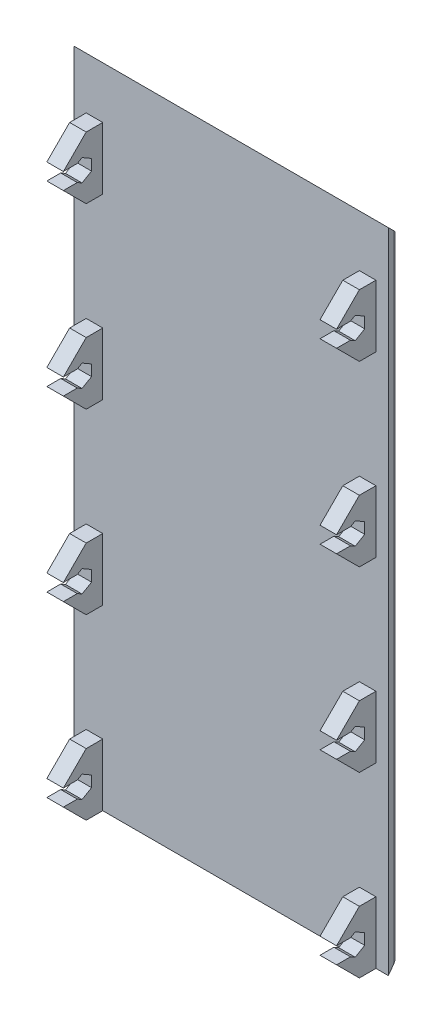
SolidWorks part; units mm, degrees
ref_plane "Front Plane" through (0, 0, 0) normal (0, 0, 1) x (1, 0, 0)
ref_plane "Top Plane" through (0, 0, 0) normal (0, 1, 0) x (1, 0, 0)
ref_plane "Right Plane" through (0, 0, 0) normal (1, 0, 0) x (0, 0, -1)
sketch "Sketch1" plane through (0, 0, 0) normal (0, 1, 0) x (1, 0, 0)
  line L0 (-9.2151, 0) -> (-9.2151, -10)
  line L1 (-9.2151, -10) -> (-5.2151, -10)
  line L2 (-5.2151, -10) -> (-5.2151, 0)
  line L3 (-5.2151, 0) -> (56.7849, 0)
  line L4 (56.7849, 0) -> (56.7849, -10)
  line L5 (56.7849, -10) -> (60.7849, -10)
  line L6 (60.7849, -10) -> (60.7849, 0)
  line L7 (60.7849, 0) -> (63.7849, 0)
  line L8 (-9.2151, 0) -> (-12.2151, 0)
  line L9 (-12.2151, 0) -> (-8.1737, 7)
  line L10 (-8.1737, 7) -> (59.7434, 7)
  line L11 (59.7434, 7) -> (63.7849, 0)
  line L12 (25.7849, 7) -> (25.7849, 0) construction
  dimension "D1" = 3
  dimension "D2" = 10
  dimension "D3" = 70
  dimension "D4" = 7
  dimension "D5" = 4
  dimension "D6" = 60
extrude "Boss-Extrude1" add sketch "Sketch1" along normal blind 156.5
sketch "Sketch4" plane through (60.7849, 0, 0) normal (1, 0, 0) x (0, 0, -1)
  line L0 (0, 156.5) -> (0, 0) construction
  line L1 (-37.5185, 156.5) -> (0, 156.5)
  line L2 (-37.5185, 156.5) -> (-37.5185, 144)
  line L3 (-37.5185, 144) -> (0, 144)
  line L4 (0, 156.5) -> (0, 144)
  line L5 (-37.5185, 156.5) -> (0, 144) construction
  line L6 (-37.5185, 144) -> (0, 156.5) construction
  line L7 (-10, 156.5) -> (0, 156.5) construction
  point P0 (-18.7592, 150.25)
  dimension "D1" = 12.5
extrude "Cut-Extrude1" cut sketch "Sketch4" against normal through all
sketch "Sketch5" plane through (60.7849, 0, 0) normal (1, 0, 0) x (0, 0, -1)
  line L0 (0, 156.5) -> (0, 0) construction
  line L1 (-33.3149, 129) -> (0, 129)
  line L2 (-33.3149, 129) -> (-33.3149, 101)
  line L3 (-33.3149, 101) -> (0, 101)
  line L4 (0, 129) -> (0, 101)
  line L5 (-33.3149, 129) -> (0, 101) construction
  line L6 (-33.3149, 101) -> (0, 129) construction
  line L7 (-10, 144) -> (0, 144) construction
  point P0 (-16.6574, 115)
  dimension "D1" = 28
  dimension "D2" = 15
extrude "Cut-Extrude2" cut sketch "Sketch5" against normal through all
sketch "Sketch6" plane through (0, 0, 0) normal (1, 0, 0) x (0, 0, -1)
  line L0 (-10, 144) -> (-10, 129) construction
  line L1 (-2.7, 137.8279) -> (-5, 139.1558)
  line L2 (-5, 139.1558) -> (-7.3, 137.8279)
  line L3 (-7.3, 137.8279) -> (-7.3, 135.1721)
  line L4 (-7.3, 135.1721) -> (-5, 133.8442)
  line L5 (-5, 133.8442) -> (-2.7, 135.1721)
  line L6 (-2.7, 135.1721) -> (-2.7, 137.8279)
  line L7 (-10, 144) -> (0, 144) construction
  line L8 (-6.15, 138.4919) -> (-10, 138.4919)
  line L9 (-6.15, 134.5081) -> (-10, 134.5081)
  line L10 (-10, 134.5081) -> (-10, 138.4919)
  circle A1 centre (-5, 136.5) radius 2.3 construction
  dimension "D1" = 4.6
  dimension "D2" = 7.5
  dimension "D3" = 5
extrude "Cut-Extrude3" cut sketch "Sketch6" against normal through all and the other way through all contours L10 L9 L4 L3 L2 L8 | L5 L6 L1 L2 L3 L4 region at (0, 136.5, 5) region at (0, 136.5, 8.5351)
pattern_linear "LPattern1" count 4 spacing 43 along (0, -1, 0) of "Cut-Extrude2", "Cut-Extrude3"
chamfer "Chamfer3" distance 7 angle 45 1 edges at (25.7849, 156.5, -7)
fillet "Fillet1" radius 8 2 edges at (-8.1737, 74.75, -7) (59.7434, 74.75, -7)
chamfer "Chamfer5" distance 6 angle 45 16 edges at (58.7849, 43, 10) (58.7849, 144, 10) (58.7849, 129, 10) (-7.2151, 144, 10) (-7.2151, 129, 10) (-7.2151, 101, 10) (-7.2151, 86, 10) (58.7849, 101, 10) (58.7849, 86, 10) (58.7849, 58, 10) (58.7849, 0, 10) (58.7849, 15, 10) (-7.2151, 0, 10) (-7.2151, 15, 10) (-7.2151, 58, 10) (-7.2151, 43, 10)
sketch "Sketch7" plane through (0, 0, -7) normal (0, 0, -1) x (-1, 0, 0)
  line L0 (-11.7849, 94.4158) -> (-39.7849, 94.4158) construction
  line L1 (-11.7849, 94.4158) -> (-11.7849, 55.0842) construction
  line L2 (-39.7849, 94.4158) -> (-39.7849, 55.0842) construction
  line L3 (-11.7849, 55.0842) -> (-39.7849, 55.0842) construction
  line L4 (-11.7849, 94.4158) -> (-11.7849, 87.9932)
  line L5 (-11.7849, 94.4158) -> (-39.7849, 94.4158)
  line L6 (-11.7849, 87.4158) -> (-39.7849, 87.4158) construction
  line L7 (-39.7849, 94.4158) -> (-39.7849, 87.9932)
  line L8 (3.5549, 55.0842) -> (-11.7849, 55.0842) construction
  line L9 (-11.7849, 79.3329) -> (-18.2849, 75.5801)
  line L10 (-12.2849, 87.1271) -> (-25.7849, 79.3329)
  line L11 (-25.7849, 79.3329) -> (-39.2849, 87.1271)
  line L14 (-25.7849, 71.25) -> (-39.2849, 63.4558)
  line L15 (-11.7849, 79.3329) -> (-11.7849, 65.5842)
  line L16 (-39.7849, 62.5897) -> (-39.7849, 55.0842)
  line L17 (-39.7849, 55.0842) -> (-32.7849, 59.1256)
  line L18 (-32.7849, 59.1256) -> (-32.7849, 65.5842)
  line L19 (-18.7849, 74.7141) -> (-18.7849, 65.5842)
  line L20 (-11.7849, 65.5842) -> (-32.7849, 65.5842) construction
  line L21 (-25.7849, 71.25) -> (-25.7849, 65.5842)
  line L22 (-18.7849, 65.5842) -> (-25.7849, 65.5842) construction
  line L23 (-32.7849, 83.3744) -> (-39.2849, 79.6216)
  line L24 (3.5549, 0) -> (3.5549, 149.5) construction
  line L25 (-39.7849, 78.7556) -> (-39.7849, 71.8274)
  line L26 (-25.7849, 79.3329) -> (-32.7849, 75.2915)
  line L27 (-32.7849, 75.2915) -> (-25.7849, 71.25)
  line L28 (-11.7849, 55.0842) -> (-39.7849, 55.0842) construction
  line L29 (-39.7849, 55.0842) -> (-55.1246, 55.0842) construction
  line L30 (-55.1246, 149.5) -> (-55.1246, 0) construction
  line L31 (-11.7849, 149.5) -> (-11.7849, 94.4158) construction
  line L32 (3.5549, 149.5) -> (-55.1246, 149.5) construction
  line L33 (-11.7849, 55.0842) -> (-11.7849, 0) construction
  line L34 (-55.1246, 0) -> (3.5549, 0) construction
  line L35 (-39.2849, 70.9613) -> (-32.7849, 67.2085)
  line L38 (-32.7849, 59.1256) -> (-31.2016, 60.0397)
  arc A0 (-11.7849, 65.5842) -> (-32.7849, 65.5842) centre (-22.2849, 65.5842) cw
  arc A1 (-18.7849, 65.5842) -> (-25.7849, 65.5842) centre (-22.2849, 65.5842) cw
  arc A3 (-18.2849, 75.5801) -> (-18.7849, 74.7141) centre (-17.7849, 74.7141) ccw
  arc A4 (-11.7849, 87.9932) -> (-12.2849, 87.1271) centre (-12.7849, 87.9932) cw
  arc A5 (-39.2849, 87.1271) -> (-39.7849, 87.9932) centre (-38.7849, 87.9932) cw
  arc A7 (-39.7849, 71.8274) -> (-39.2849, 70.9613) centre (-38.7849, 71.8274) ccw
  arc A8 (-39.2849, 79.6216) -> (-39.7849, 78.7556) centre (-38.7849, 78.7556) ccw
  arc A9 (-39.2849, 63.4558) -> (-39.7849, 62.5897) centre (-38.7849, 62.5897) ccw
  point P10 (0, 0)
  point P43 (-39.7849, 63.1671)
  point P50 (-39.7849, 63.1671)
  point P52 (-39.7849, 63.1671)
  point P57 (-39.7849, 71.25)
  point P60 (-39.7849, 79.3329)
  dimension "D11" = 7
  dimension "D12" = 7
  dimension "D10" = 7
  dimension "D14" = 1
  dimension "D16" = 1
  dimension "D6" = 1
  dimension "D13" = 1
  dimension "D2" = 7
  dimension "D3" = 7
  dimension "D4" = 30
  dimension "D5" = 30
  dimension "D7" = 7
  dimension "D8" = 7
  dimension "D9" = 7
  dimension "D15" = 30
extrude "Cut-Extrude4" cut sketch "Sketch7" against normal blind 1 contours L5 L7 L6 L4 | L6 L11 L10 | L27 L26 L11 L9 | L19 A1 L21 L9 L16 L17 L18 A0 L15 | L38 A0 L18 region at (25.7849, 88.6489, -7) region at (33.7137, 75.2915, -7) region at (26.1553, 68.4171, -7) region at (32.3046, 61.0644, -7)
fillet "Fillet2" radius 1 3 edges at (25.7849, 71.25, -6.5) (39.7849, 94.4158, -6.5) (11.7849, 94.4158, -6.5)
